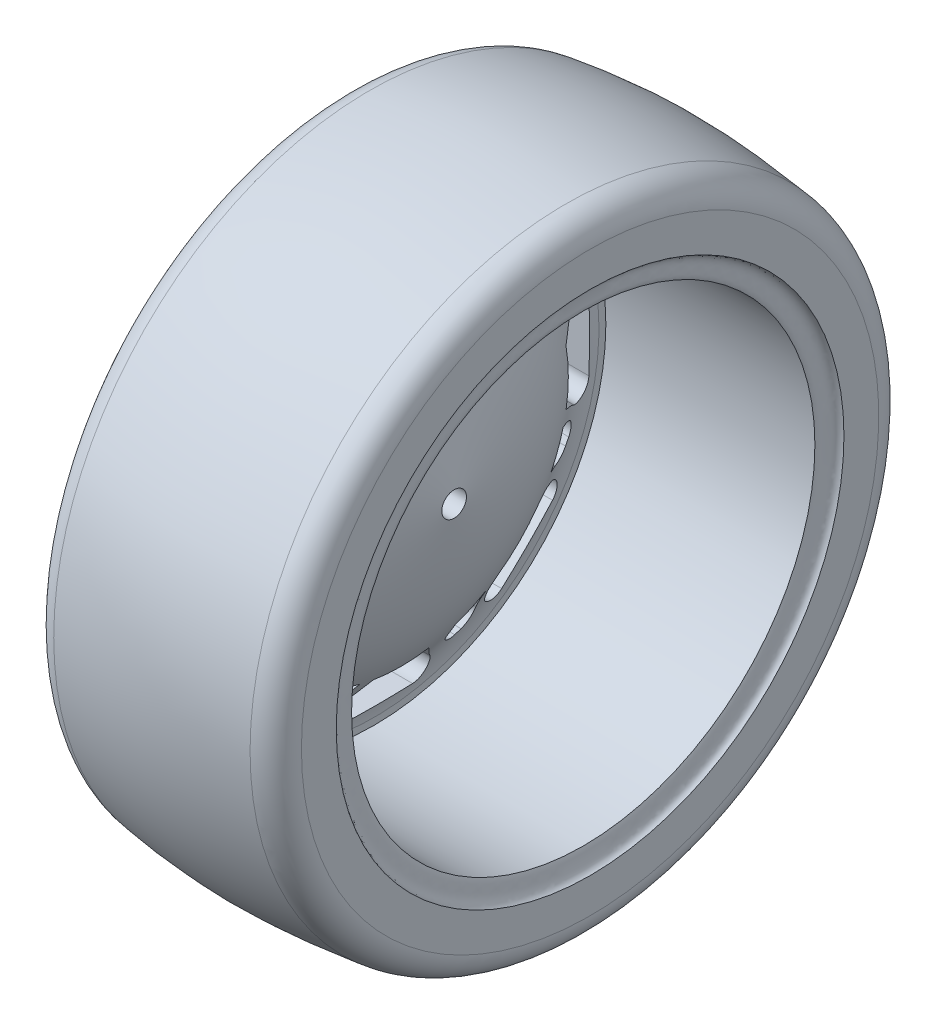
SolidWorks part; units mm, degrees
ref_plane "Front Plane" through (0, 0, 0) normal (0, 0, 1) x (1, 0, 0)
ref_plane "Top Plane" through (0, 0, 0) normal (0, 1, 0) x (1, 0, 0)
ref_plane "Right Plane" through (0, 0, 0) normal (1, 0, 0) x (0, 0, -1)
sketch "Sketch1" plane through (0, 0, 0) normal (0, 0, 1) x (1, 0, 0)
  line L0 (0, 0) -> (0, -99.3115) construction
  line L2 (-44.3922, 6.203) -> (-44.3922, -11.1159)
  line L3 (-34.1814, -14.6722) -> (42.1899, -14.6722)
  line L4 (44.697, 6.1592) -> (44.697, -6.5678)
  line L5 (-44.697, 14.6722) -> (44.697, -14.6722) construction
  line L6 (-40.2471, -13.3022) -> (44.3922, 14.6722) construction
  line L7 (-4.469, -99.3115) -> (-14.2863, -99.3115)
  line L8 (-44.3922, -11.1159) -> (-44.1265, -18.2285)
  line L13 (-4.469, -97.4088) -> (-4.469, -99.3115)
  line L14 (-34.1814, -17.182) -> (-34.1814, -14.6722)
  line L15 (42.1899, -14.6722) -> (-25.2592, -14.6722)
  line L16 (-14.2863, -99.3115) -> (0, -99.3115) construction
  arc A0 (44.697, 6.1592) -> (35.8627, 16.091) centre (34.697, 6.1592) ccw
  arc A1 (-44.3922, 6.203) -> (-35.8647, 16.094) centre (-34.3922, 6.203) cw
  arc A2 (-25.2592, -14.6722) -> (-32.09, -25.5405) centre (-25.2592, -22.2529) ccw
  spline S0 degree 3 poles (-35.8647, 16.094) (-23.9373, 17.8698) (0.0359, 19.8291) (23.8631, 17.4993) (35.8627, 16.091) knots 0.096298 0.096298 0.096298 0.096298 0.500124 0.90393 0.90393 0.90393 0.90393
  spline S1 degree 3 poles (-44.1265, -18.2285) (-43.5278, -23.9185) (-35.3247, -46.4387) (-24.7718, -45.2084) (-14.2863, -99.3115) knots 0.038573 0.038573 0.038573 0.038573 0.225612 1 1 1 1
  spline S2 degree 3 poles (44.697, -6.5678) (41.4021, -8.0833) (43.246, -12.2752) (42.1899, -14.6722) knots 0 0 0 0 1 1 1 1
  spline S3 degree 1 poles (-34.1814, -17.182) (-4.469, -97.4088) knots 0 0 1 1 construction
  spline S4 degree 3 poles (-34.1814, -17.182) (-34.1451, -17.5265) (-34.0604, -18.2247) (-33.859, -19.532) (-33.5473, -21.066) (-33.0954, -22.7526) (-32.6486, -24.1031) (-32.2565, -25.1376) (-31.8663, -26.087) (-31.1665, -27.6389) (-30.1043, -29.6619) (-28.7375, -31.8744) (-26.6336, -34.9534) (-23.9665, -38.6798) (-20.9823, -43.6005) (-18.6857, -47.9724) (-16.371, -53.1459) (-14.0488, -59.2706) (-12.1004, -65.3172) (-10.5273, -70.8186) (-9.3388, -75.3022) (-8.1402, -80.1689) (-7.1317, -84.566) (-6.319, -88.2998) (-5.7054, -91.2159) (-5.0912, -94.2328) (-4.6725, -96.3591) (-4.469, -97.4088) knots 0.038573 0.038573 0.038573 0.038573 0.053595 0.068617 0.098662 0.128707 0.158751 0.176799 0.191822 0.21884 0.27893 0.339019 0.399108 0.519286 0.579376 0.639465 0.699554 0.759643 0.819732 0.849777 0.879822 0.909866 0.939911 0.954933 0.969955 0.984978 1 1 1 1
  point P0 (0, 0)
  dimension "D2" = 10
  dimension "D1" = 10
revolve "Revolve6" add sketch "Sketch1" angle 360 about L16
sketch "Sketch2" plane through (-44.3922, 0, 0) normal (-1, 0, 0) x (0, 0, 1)
  line L0 (46.072, -35.1648) -> (64.689, -53.7818)
  line L1 (61.831, -62.2712) -> (46.1598, -64.4145)
  line L2 (-16.8805, -29.2372) -> (-8.1996, -41.6722)
  line L3 (17.5297, -29.3989) -> (7.964, -41.9957)
  line L4 (-12.7807, -21.3751) -> (13.5477, -21.3751)
  line L5 (37.6137, -37.8251) -> (34.9591, -52.7563)
  line L6 (77.9364, -86.5308) -> (77.9364, -112.8592)
  line L7 (69.9126, -116.8412) -> (57.3158, -107.2755)
  line L8 (70.0743, -82.431) -> (57.6393, -91.1118)
  line L9 (64.1467, -145.3835) -> (45.5297, -164.0005)
  line L10 (37.0403, -161.1425) -> (34.897, -145.4713)
  line L11 (61.4864, -136.9252) -> (46.5552, -134.2706)
  line L12 (12.7807, -177.2479) -> (-13.5477, -177.2479)
  line L13 (-17.5297, -169.2241) -> (-7.964, -156.6273)
  line L14 (16.8805, -169.3858) -> (8.1996, -156.9508)
  line L15 (-46.072, -163.4582) -> (-64.689, -144.8412)
  line L16 (-61.831, -136.3518) -> (-46.1598, -134.2084)
  line L17 (-37.6137, -160.7979) -> (-34.9591, -145.8666)
  line L18 (-77.9364, -112.0922) -> (-77.9364, -85.7638)
  line L19 (-69.9126, -81.7818) -> (-57.3158, -91.3475)
  line L20 (-70.0743, -116.192) -> (-57.6393, -107.5111)
  line L21 (-64.1467, -53.2394) -> (-45.5297, -34.6225)
  line L22 (-37.0403, -37.4805) -> (-34.897, -53.1517)
  line L23 (-61.4864, -61.6978) -> (-46.5552, -64.3524)
  line L24 (0, -97.4088) -> (0, -17.182) construction
  circle A0 centre (0, -99.3115) radius 81.083 construction
  arc A1 (7.964, -41.9957) -> (-8.1996, -41.6722) centre (0, -35.948) cw
  arc A2 (-12.7807, -21.3751) -> (-16.8805, -29.2372) centre (-12.7807, -26.3751) ccw
  arc A3 (17.5297, -29.3989) -> (13.5477, -21.3751) centre (13.5477, -26.3751) ccw
  arc A4 (61.831, -62.2712) -> (64.689, -53.7818) centre (61.1535, -57.3173) ccw
  arc A5 (46.072, -35.1648) -> (37.6137, -37.8251) centre (42.5365, -38.7003) ccw
  arc A6 (46.1598, -64.4145) -> (34.9591, -52.7563) centre (44.8047, -54.5068) cw
  arc A7 (69.9126, -116.8412) -> (77.9364, -112.8592) centre (72.9364, -112.8592) ccw
  arc A8 (77.9364, -86.5308) -> (70.0743, -82.431) centre (72.9364, -86.5308) ccw
  arc A9 (57.3158, -107.2755) -> (57.6393, -91.1118) centre (63.3635, -99.3115) cw
  arc A10 (37.0403, -161.1425) -> (45.5297, -164.0005) centre (41.9942, -160.465) ccw
  arc A11 (64.1467, -145.3835) -> (61.4864, -136.9252) centre (60.6112, -141.848) ccw
  arc A12 (34.897, -145.4713) -> (46.5552, -134.2706) centre (44.8047, -144.1162) cw
  arc A13 (-17.5297, -169.2241) -> (-13.5477, -177.2479) centre (-13.5477, -172.2479) ccw
  arc A14 (12.7807, -177.2479) -> (16.8805, -169.3858) centre (12.7807, -172.2479) ccw
  arc A15 (-7.964, -156.6273) -> (8.1996, -156.9508) centre (0, -162.6749) cw
  arc A16 (-61.831, -136.3518) -> (-64.689, -144.8412) centre (-61.1535, -141.3056) ccw
  arc A17 (-46.072, -163.4582) -> (-37.6137, -160.7979) centre (-42.5365, -159.9226) ccw
  arc A18 (-46.1598, -134.2084) -> (-34.9591, -145.8666) centre (-44.8047, -144.1162) cw
  arc A19 (-69.9126, -81.7818) -> (-77.9364, -85.7638) centre (-72.9364, -85.7638) ccw
  arc A20 (-77.9364, -112.0922) -> (-70.0743, -116.192) centre (-72.9364, -112.0922) ccw
  arc A21 (-57.3158, -91.3475) -> (-57.6393, -107.5111) centre (-63.3635, -99.3115) cw
  arc A22 (-37.0403, -37.4805) -> (-45.5297, -34.6225) centre (-41.9942, -38.158) ccw
  arc A23 (-64.1467, -53.2394) -> (-61.4864, -61.6978) centre (-60.6112, -56.775) ccw
  arc A24 (-34.897, -53.1517) -> (-46.5552, -64.3524) centre (-44.8047, -54.5068) cw
  point P13 (-0.3399, -52.9309)
  point P15 (-22.369, -21.3751)
  point P18 (23.6228, -21.3751)
  dimension "D1" = 10
  dimension "D2" = 5
  dimension "D3" = 5
  dimension "D4" = 8
extrude "Cut-Extrude1" cut sketch "Sketch2" against normal blind 20
sketch "Sketch3" plane through (-44.3922, 0, 0) normal (-1, 0, 0) x (0, 0, 1)
  line L0 (-27.0156, -30.1375) -> (-29.1725, -31.4595)
  line L1 (-30.8227, -38.3353) -> (-18.9662, -57.6801)
  line L2 (-12.0903, -59.3303) -> (-9.9335, -58.0084)
  line L3 (-8.2833, -51.1326) -> (-20.1398, -31.7877)
  line L4 (28.2105, -59.3867) -> (33.5055, -37.324)
  line L5 (29.8105, -31.2952) -> (27.3506, -30.7048)
  line L6 (21.3218, -34.3999) -> (16.0267, -56.4626)
  line L7 (19.7218, -62.4914) -> (22.1817, -63.0818)
  line L8 (48.1789, -91.0282) -> (67.5238, -79.1717)
  line L9 (69.174, -72.2959) -> (67.852, -70.139)
  line L10 (60.9762, -68.4888) -> (41.6313, -80.3453)
  line L11 (39.9812, -87.2211) -> (41.3031, -89.378)
  line L12 (39.9248, -127.522) -> (61.9875, -132.817)
  line L13 (68.0163, -129.122) -> (68.6067, -126.662)
  line L14 (64.9116, -120.6332) -> (42.8489, -115.3382)
  line L15 (36.8201, -119.0333) -> (36.2297, -121.4932)
  line L16 (8.2833, -147.4904) -> (20.1398, -166.8353)
  line L17 (27.0156, -168.4855) -> (29.1725, -167.1635)
  line L18 (30.8227, -160.2877) -> (18.9662, -140.9428)
  line L19 (12.0903, -139.2926) -> (9.9335, -140.6146)
  line L20 (-28.2105, -139.2363) -> (-33.5055, -161.299)
  line L21 (-29.8105, -167.3278) -> (-27.3506, -167.9182)
  line L22 (-21.3218, -164.2231) -> (-16.0267, -142.1604)
  line L23 (-19.7218, -136.1316) -> (-22.1817, -135.5412)
  line L24 (-48.1789, -107.5948) -> (-67.5238, -119.4513)
  line L25 (-69.174, -126.3271) -> (-67.852, -128.484)
  line L26 (-60.9762, -130.1342) -> (-41.6313, -118.2776)
  line L27 (-39.9812, -111.4018) -> (-41.3031, -109.2449)
  line L28 (-39.9248, -71.101) -> (-61.9875, -65.8059)
  line L29 (-68.0163, -69.501) -> (-68.6067, -71.9609)
  line L30 (-64.9116, -77.9897) -> (-42.8489, -83.2848)
  line L31 (-36.8201, -79.5897) -> (-36.2297, -77.1298)
  arc A0 (-30.8227, -38.3353) -> (-29.1725, -31.4595) centre (-26.5597, -35.7225) cw
  arc A1 (-12.0903, -59.3303) -> (-18.9662, -57.6801) centre (-14.7032, -55.0673) cw
  arc A2 (-8.2833, -51.1326) -> (-9.9335, -58.0084) centre (-12.5463, -53.7454) cw
  arc A3 (-20.1398, -31.7877) -> (-27.0156, -30.1375) centre (-24.4028, -34.4005) ccw
  arc A4 (33.5055, -37.324) -> (29.8105, -31.2952) centre (28.6436, -36.1571) ccw
  arc A5 (28.2105, -59.3867) -> (22.1817, -63.0818) centre (23.3486, -58.2198) cw
  arc A6 (21.3218, -34.3999) -> (27.3506, -30.7048) centre (26.1837, -35.5667) cw
  arc A7 (19.7218, -62.4914) -> (16.0267, -56.4626) centre (20.8886, -57.6294) cw
  arc A8 (67.5238, -79.1717) -> (69.174, -72.2959) centre (64.911, -74.9087) ccw
  arc A9 (48.1789, -91.0282) -> (41.3031, -89.378) centre (45.5661, -86.7652) cw
  arc A10 (60.9762, -68.4888) -> (67.852, -70.139) centre (63.589, -72.7518) cw
  arc A11 (39.9812, -87.2211) -> (41.6313, -80.3453) centre (44.2442, -84.6083) cw
  arc A12 (61.9875, -132.817) -> (68.0163, -129.122) centre (63.1544, -127.9551) ccw
  arc A13 (39.9248, -127.522) -> (36.2297, -121.4932) centre (41.0917, -122.66) cw
  arc A14 (64.9116, -120.6332) -> (68.6067, -126.662) centre (63.7448, -125.4952) cw
  arc A15 (36.8201, -119.0333) -> (42.8489, -115.3382) centre (41.682, -120.2001) cw
  arc A16 (20.1398, -166.8353) -> (27.0156, -168.4855) centre (24.4028, -164.2225) ccw
  arc A17 (8.2833, -147.4904) -> (9.9335, -140.6146) centre (12.5463, -144.8776) cw
  arc A18 (30.8227, -160.2877) -> (29.1725, -167.1635) centre (26.5597, -162.9005) cw
  arc A19 (12.0903, -139.2926) -> (18.9662, -140.9428) centre (14.7032, -143.5556) cw
  arc A20 (-33.5055, -161.299) -> (-29.8105, -167.3278) centre (-28.6436, -162.4659) ccw
  arc A21 (-28.2105, -139.2363) -> (-22.1817, -135.5412) centre (-23.3486, -140.4031) cw
  arc A22 (-21.3218, -164.2231) -> (-27.3506, -167.9182) centre (-26.1837, -163.0562) cw
  arc A23 (-19.7218, -136.1316) -> (-16.0267, -142.1604) centre (-20.8886, -140.9935) cw
  arc A24 (-67.5238, -119.4513) -> (-69.174, -126.3271) centre (-64.911, -123.7143) ccw
  arc A25 (-48.1789, -107.5948) -> (-41.3031, -109.2449) centre (-45.5661, -111.8578) cw
  arc A26 (-60.9762, -130.1342) -> (-67.852, -128.484) centre (-63.589, -125.8712) cw
  arc A27 (-39.9812, -111.4018) -> (-41.6313, -118.2776) centre (-44.2442, -114.0146) cw
  arc A28 (-61.9875, -65.8059) -> (-68.0163, -69.501) centre (-63.1544, -70.6679) ccw
  arc A29 (-39.9248, -71.101) -> (-36.2297, -77.1298) centre (-41.0917, -75.9629) cw
  arc A30 (-64.9116, -77.9897) -> (-68.6067, -71.9609) centre (-63.7448, -73.1278) cw
  arc A31 (-36.8201, -79.5897) -> (-42.8489, -83.2848) centre (-41.682, -78.4228) cw
  dimension "D1" = 5
  dimension "D2" = 8
extrude "Cut-Extrude2" cut sketch "Sketch3" against normal blind 20
scale "Scale1" scale about centroid uniform scaling yes scale factor 0.5
sketch "Sketch4" plane through (-3.365, 0, 0) normal (1, 0, 0) x (0, 0, -1)
  circle A0 centre (0, -99.3115) radius 2.25
  point P2 (0, 0)
  dimension "D1" = 4.5
extrude "Cut-Extrude3" cut sketch "Sketch4" against normal through all both and the other way through all
